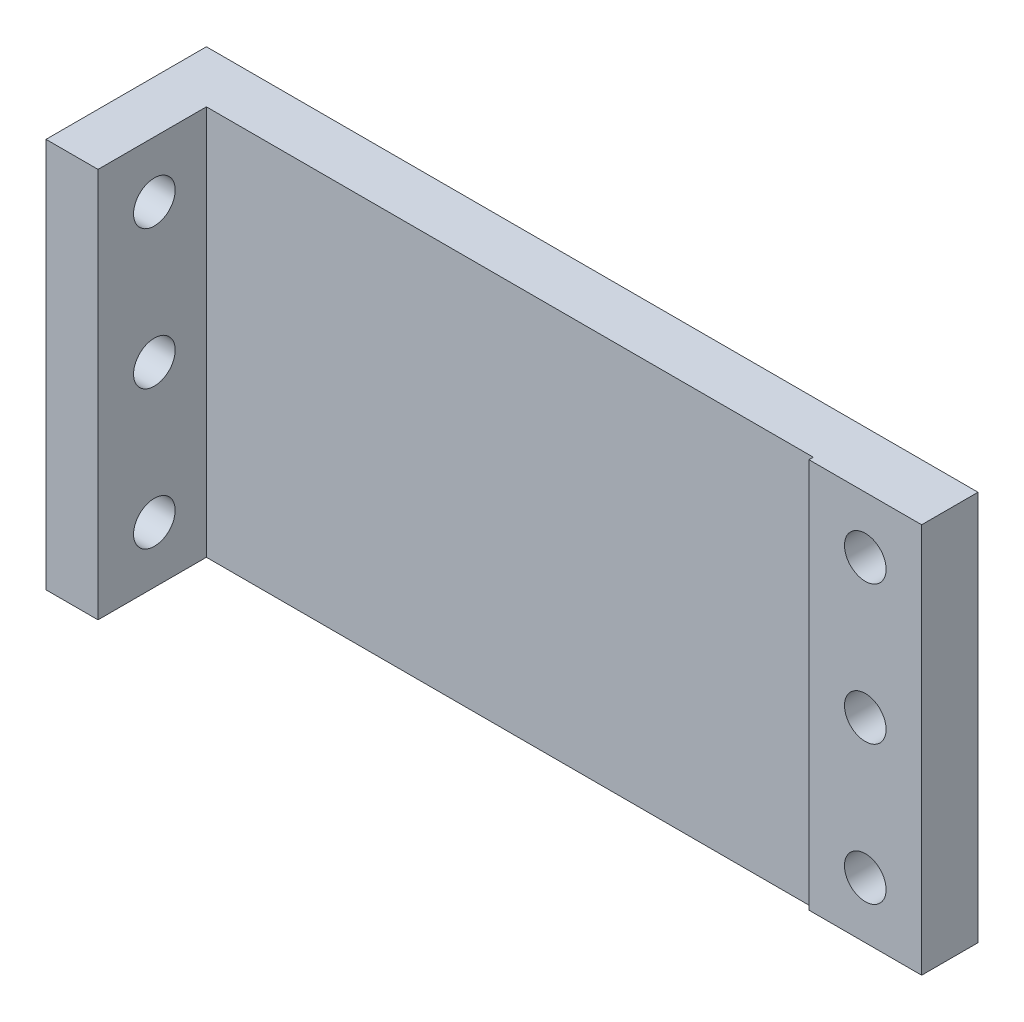
SolidWorks part; units mm, degrees
ref_plane "Plano frontal" through (0, 0, 0) normal (0, 0, 1) x (1, 0, 0)
ref_plane "Plano superior" through (0, 0, 0) normal (0, 1, 0) x (1, 0, 0)
ref_plane "Plano direito" through (0, 0, 0) normal (1, 0, 0) x (0, 0, -1)
sketch "Esboço1" plane through (0, 0, 0) normal (0, 0, 1) x (1, 0, 0)
  line L0 (-16, 3.25) -> (-16, -3.25) construction
  line L1 (-16.25, -11.25) -> (25.25, -11.25)
  line L2 (-16.25, -11.25) -> (-16.25, 11.25)
  line L3 (-16.25, 11.25) -> (25.25, 11.25)
  line L4 (25.25, -11.25) -> (25.25, 11.25)
  line L6 (22, -8) -> (22, -11.25) construction
  line L7 (22, -8) -> (25.25, -8) construction
  line L9 (22, 8) -> (22, 11.25) construction
  line L11 (25.5, -8.2779) -> (25.5, 29.7721) construction
  dimension "D1" = 0.25
  dimension "D2" = 0.25
extrude "Ressalto-extrusão1" add sketch "Esboço1" against normal blind 3
sketch "Esboço2" plane through (-16.25, 0, 0) normal (-1, 0, 0) x (0, 0, 1)
  line L1 (-3, -11.25) -> (6.25, -11.25)
  line L2 (-3, -11.25) -> (-3, 11.25)
  line L3 (-3, 11.25) -> (6.25, 11.25)
  line L4 (6.25, -11.25) -> (6.25, 11.25)
  line L5 (6.5, 29.8) -> (6.5, 13.8) construction
  line L6 (-3, 11.25) -> (0, 11.25) construction
  dimension "D1" = 0.25
extrude "Ressalto-extrusão2" add sketch "Esboço2" along normal blind 3
sketch "Esboço3" plane through (0, 0, -3) normal (0, 0, 1) x (1, 0, 0)
  line L0 (25.25, 11.25) -> (-16.25, 11.25) construction
  line L1 (25.25, -11.25) -> (18.75, -11.25)
  line L2 (25.25, -11.25) -> (25.25, 11.25)
  line L3 (25.25, 11.25) -> (18.75, 11.25)
  line L4 (18.75, -11.25) -> (18.75, 11.25)
  line L5 (18.75, 16) -> (25.25, 16) construction
  circle A0 centre (22, 16) radius 1.25 construction
  point P9 (22, 16)
extrude "Ressalto-extrusão3" add sketch "Esboço3" along normal offset from surface (3.25 mm away) 0.25
hole_wizard "Rebaixo para parafuso com cabeça redonda de M21" positions "Esboço4" profile "Esboço5" counterbore size "M2" standard "DIN" end condition through all
sketch "Esboço4" plane through (-19.25, 0, 0) normal (-1, 0, 0) x (0, 0, 1)
  circle A0 centre (3, 8) radius 1.25 construction
  circle A1 centre (3, -8) radius 1.25 construction
  circle A2 centre (3, 0) radius 1.25 construction
  point P0 (3, 8)
  point P7 (3, -8)
  point P13 (3, 0)
  point P16 (0, 0)
sketch "Esboço5" plane through (-19.25, 8, 3) normal (0, 1, 0) x (0, 0, 1)
  line L0 (0, 0) -> (0, 44.5)
  line L1 (0, 44.5) -> (1.2, 44.5)
  line L3 (1.2, 44.5) -> (1.2, 0.7)
  line L4 (1.2, 0.7) -> (2.2, 0.7)
  line L5 (2.2, 0.7) -> (2.2, 0)
  line L7 (2.2, 0) -> (0, 0)
  line L11 (0, -6.35) -> (0, 107.95) construction
  dimension "Thru Hole Dia." = 2.4
  dimension "Thru Hole Depth" = 44.5
  dimension "C'Bore Dia." = 4.4
  dimension "C'Bore Depth" = 0.7
hole_wizard "Rebaixo para parafuso com cabeça redonda de M22" positions "Esboço6" profile "Esboço7" counterbore size "M2" standard "DIN" end condition through all
sketch "Esboço6" plane through (0, 0, -3) normal (0, 0, -1) x (-1, 0, 0)
  circle A0 centre (-22, 8) radius 1.25 construction
  point P0 (-22, 8)
  point P6 (-22, 0)
  point P9 (-22, -8)
sketch "Esboço7" plane through (22, 8, -3) normal (1, 0, 0) x (0, 1, 0)
  line L0 (0, 0) -> (0, 9.25)
  line L1 (0, 9.25) -> (1.2, 9.25)
  line L3 (1.2, 9.25) -> (1.2, 0.7)
  line L4 (1.2, 0.7) -> (2.2, 0.7)
  line L5 (2.2, 0.7) -> (2.2, 0)
  line L7 (2.2, 0) -> (0, 0)
  line L11 (0, -6.35) -> (0, 107.95) construction
  dimension "Thru Hole Dia." = 2.4
  dimension "Thru Hole Depth" = 9.25
  dimension "C'Bore Dia." = 4.4
  dimension "C'Bore Depth" = 0.7
move or copy body "Corpo-Mover/Copiar1" [suppressed] bodies to move or copy 102 103
